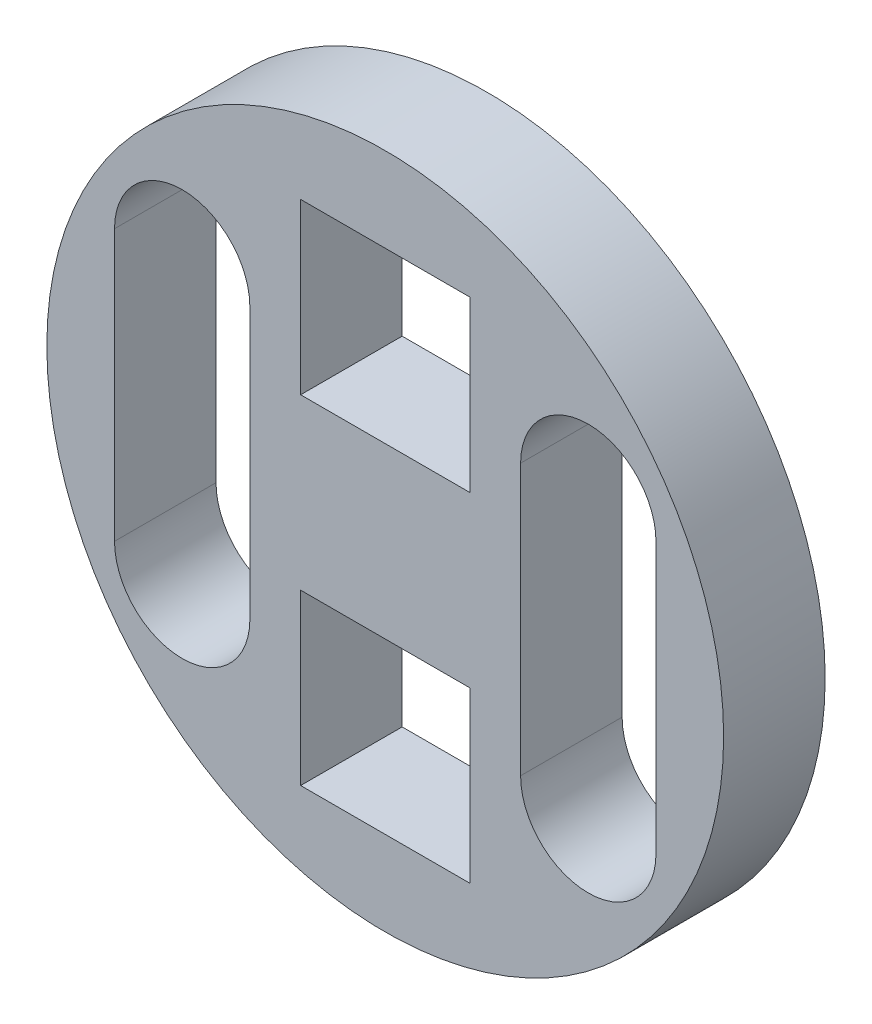
SolidWorks part; units mm, degrees
ref_plane "Plan de face" through (0, 0, 0) normal (0, 0, 1) x (1, 0, 0)
ref_plane "Plan de dessus" through (0, 0, 0) normal (0, 1, 0) x (1, 0, 0)
ref_plane "Plan de droite" through (0, 0, 0) normal (1, 0, 0) x (0, 0, -1)
sketch "Esquisse1" plane through (0, 0, 0) normal (0, 0, 1) x (1, 0, 0)
  line L0 (6, 4) -> (6, -4) construction
  line L1 (8, 4) -> (8, -4)
  line L2 (4, 4) -> (4, -4)
  line L3 (-6, 4) -> (-6, -4) construction
  line L4 (-8, 4) -> (-8, -4)
  line L5 (-4, 4) -> (-4, -4)
  circle A2 centre (0, 0) radius 10
  arc A3 (8, 4) -> (4, 4) centre (6, 4) ccw
  arc A4 (4, -4) -> (8, -4) centre (6, -4) ccw
  arc A5 (-8, 4) -> (-4, 4) centre (-6, 4) cw
  arc A6 (-4, -4) -> (-8, -4) centre (-6, -4) cw
  point P3 (6, 0)
  point P10 (0, 0)
  point P13 (-6, 0)
  line B0 (0, -2.5) -> (0, 2.5) construction
  line B1 (-2.5, -2.5) -> (-2.5, -7.5)
  line B2 (-2.5, -2.5) -> (2.5, -2.5)
  line B3 (2.5, -2.5) -> (2.5, -7.5)
  line B4 (-2.5, -7.5) -> (2.5, -7.5)
  line B5 (-2.5, 2.5) -> (-2.5, 7.5)
  line B6 (-2.5, 2.5) -> (2.5, 2.5)
  line B7 (2.5, 2.5) -> (2.5, 7.5)
  line B8 (-2.5, 7.5) -> (2.5, 7.5)
  line B9 (0, 0) -> (-6.301, 0) construction
  circle B10 centre (0, 0) radius 1.5 construction
  dimension "D1" = 20
  dimension "D2" = 8
  dimension "D3" = 8
  dimension "D4" = 4
  dimension "D5" = 6
sketch_block_instance "Trou M3 plots 5mm-52"
sketch_block "Trou M3 plots 5mm" parameters "D2"=3, "D5"=3, "D1"=5, "D3"=5, "D4"=8
extrude "Boss.-Extru.1" add sketch "Esquisse1" along normal blind 3
